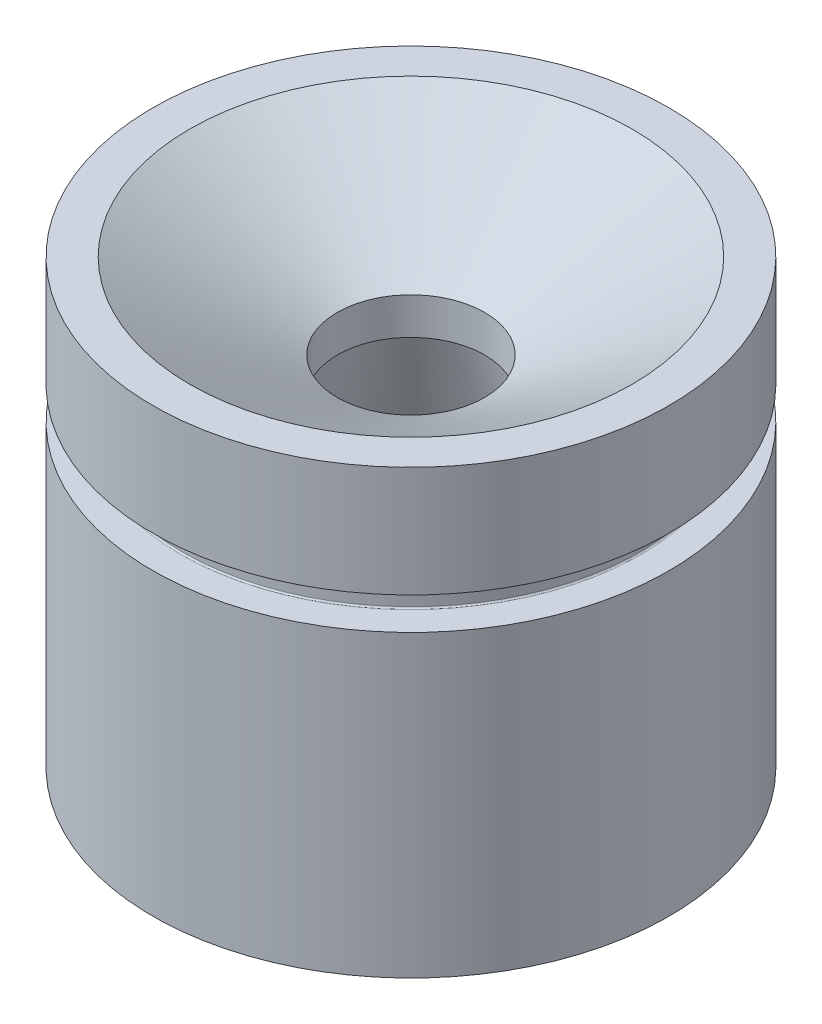
SolidWorks part; units mm, degrees
material "C (Graphite)"
ref_plane "Front Plane" through (0, 0, 0) normal (0, 0, 1) x (1, 0, 0)
ref_plane "Top Plane" through (0, 0, 0) normal (0, 1, 0) x (1, 0, 0)
ref_plane "Right Plane" through (0, 0, 0) normal (1, 0, 0) x (0, 0, -1)
sketch "Sketch1" plane through (0, 0, 0) normal (0, 0, 1) x (1, 0, 0)
  line L0 (0, 0) -> (0, 76.2) construction
  line L1 (0, 0) -> (-44.45, 0) construction
  line L2 (-44.45, 0) -> (-44.45, 76.2)
  line L4 (-12.7, 61.5353) -> (-12.7, 55.1853)
  line L5 (-12.7, 55.1853) -> (-28.321, 0)
  line L6 (-28.321, 0) -> (-44.45, 0)
  line L7 (-44.45, 76.2) -> (-38.1, 76.2)
  line L8 (-38.1, 76.2) -> (-12.7, 61.5353)
  dimension "D1" = 76.2
  dimension "D2" = 28.321
  dimension "D3" = 12.7
  dimension "D4" = 6.35
  dimension "D5" = 44.45
  dimension "D6" = 6.35
  dimension "D7" = 30
  dimension "D8" = 16.129
revolve "Revolve1" add sketch "Sketch1" angle 360 about L0
sketch "Sketch2" plane through (0, 0, 0) normal (0, 0, 1) x (1, 0, 0)
  line L0 (0, 0) -> (0, 121.2055) construction
  line L1 (0, 57.15) -> (-44.45, 57.15) construction
  line L3 (-44.45, 57.15) -> (-39.624, 57.15)
  line L4 (-44.45, 57.15) -> (-44.45, 51.562)
  line L5 (-44.45, 51.562) -> (-39.624, 51.562)
  line L6 (-39.37, 56.896) -> (-39.37, 51.816)
  line L7 (38.1, 76.2) -> (-38.1, 76.2) construction
  arc A0 (-39.624, 57.15) -> (-39.37, 56.896) centre (-39.624, 56.896) cw
  arc A1 (-39.624, 51.562) -> (-39.37, 51.816) centre (-39.624, 51.816) ccw
  point P12 (-39.37, 57.15)
  point P15 (-39.37, 51.562)
  dimension "D5" = 0.254
  dimension "D1" = 44.45
  dimension "D2" = 5.588
  dimension "D3" = 39.37
  dimension "D4" = 19.05
revolve "Cut-Revolve1" cut sketch "Sketch2" angle 360 about L0
